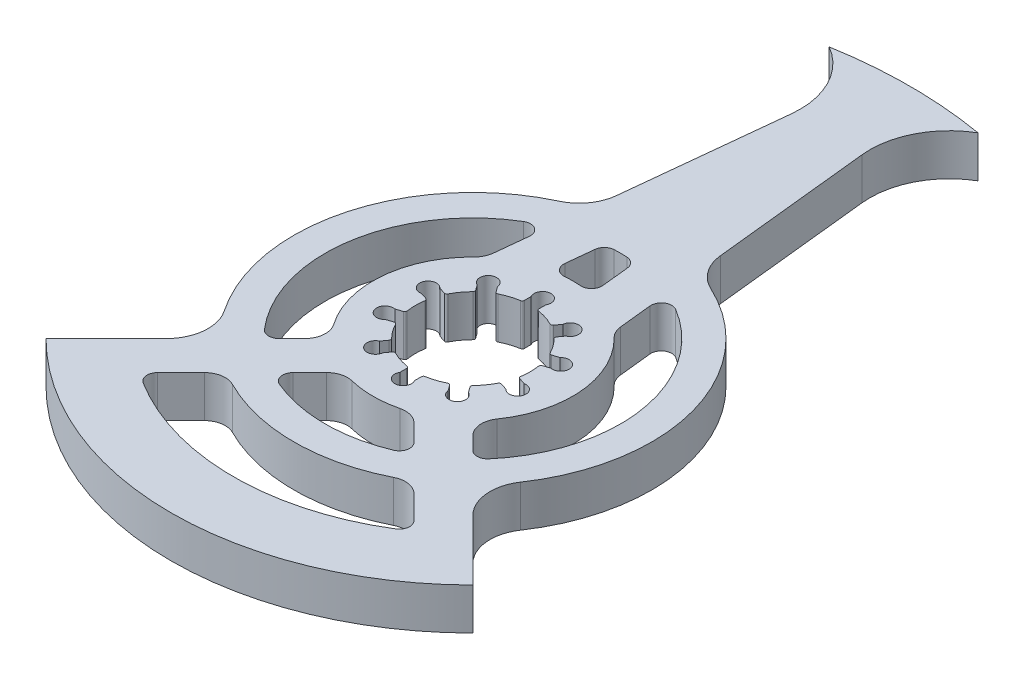
SolidWorks part; units mm, degrees
material "AISI Type A2 Tool Steel"
ref_plane "Front Plane" through (0, 0, 0) normal (0, 0, 1) x (1, 0, 0)
ref_plane "Top Plane" through (0, 0, 0) normal (0, 1, 0) x (1, 0, 0)
ref_plane "Right Plane" through (0, 0, 0) normal (1, 0, 0) x (0, 0, -1)
other "Center of Mass"
other "Bounding Box"
ref_plane "Default Plane" through (0, 2.286, 19.05) normal (0, -1, 0) x (-1, 0, 0)
sketch "Sketch1" plane through (0, 0, 0) normal (0, 1, 0) x (1, 0, 0)
  circle A0 centre (0, 0) radius 133.35 construction
  circle A1 centre (0, 0) radius 30.48
  circle A2 centre (0, 0) radius 17.4625
  dimension "D1" = 266.7
  dimension "D2" = 60.96
  dimension "D3" = 34.925
extrude "Boss-Extrude1" add sketch "Sketch1" along normal mid plane 12.7
sketch "Sketch2" plane through (0, 6.35, 0) normal (0, 1, 0) x (1, 0, 0)
  line L0 (-10.795, 107.95) -> (-19.6961, 23.2614)
  line L1 (19.6961, 23.2614) -> (10.795, 107.95)
  line L4 (0, 0) -> (0, 133.35) construction
  line L5 (-10.795, 107.95) -> (0, 107.95) construction
  line L6 (0, 107.95) -> (10.795, 107.95) construction
  line L7 (-22.6939, 131.4048) -> (0, 0) construction
  line L8 (-22.6939, 131.4048) -> (125.4677, 45.1673) construction
  circle A0 centre (0, 0) radius 133.35 construction
  circle A1 centre (0, 0) radius 133.35 construction
  arc A2 (-22.6939, 131.4048) -> (22.6939, 131.4048) centre (0, 0) cw
  arc A3 (-22.6939, 131.4048) -> (-10.795, 107.95) centre (-34.8727, 110.4807) cw
  circle A5 centre (0, 0) radius 30.48
  arc A6 (19.6961, 23.2614) -> (-19.6961, 23.2614) centre (0, 0) ccw
  arc A7 (-19.6961, 23.2614) -> (19.6961, 23.2614) centre (0, 0) ccw construction
  arc A8 (10.795, 107.95) -> (22.6939, 131.4048) centre (34.8727, 110.4807) cw
  dimension "D4" = 25.4
  dimension "D5" = 6
  dimension "D6" = 10.795
  dimension "D1" = 50
  dimension "D2" = 0
extrude "Boss-Extrude2" add sketch "Sketch2" against normal through all
sketch "Sketch3" plane through (0, 6.35, 0) normal (0, 1, 0) x (1, 0, 0)
  line L0 (-65.1069, -65.1069) -> (-21.5526, -21.5526)
  line L1 (21.5526, -21.5526) -> (65.1069, -65.1069)
  line L2 (0, -30.48) -> (0, -92.075) construction
  line L4 (-21.5526, -21.5526) -> (0, 0) construction
  line L5 (0, 0) -> (21.5526, -21.5526) construction
  arc A0 (-65.1069, -65.1069) -> (65.1069, -65.1069) centre (0, 0) ccw
  circle A1 centre (0, 0) radius 30.48 construction
  arc A3 (-21.5526, -21.5526) -> (21.5526, -21.5526) centre (0, 0) ccw
  point P13 (0, -92.075)
  dimension "D2" = 92.075
  dimension "D1" = 90
extrude "Boss-Extrude3" add sketch "Sketch3" against normal through all
sketch "Sketch5" plane through (0, 6.35, 0) normal (0, 1, 0) x (1, 0, 0)
  line L0 (0, 17.4625) -> (0, 21.2725) construction
  line L2 (-2.2225, 17.3205) -> (2.2225, 17.3205)
  line L3 (-2.2225, 17.3205) -> (-2.2225, 20.0168)
  line L5 (2.2225, 17.3205) -> (2.2225, 20.0168)
  arc A0 (2.2225, 20.0168) -> (-2.2225, 20.0168) centre (0, 21.2725) ccw
  circle A1 centre (0, 0) radius 17.4625 construction
  circle A2 centre (0, 21.2725) radius 4.5847 construction
  dimension "D2" = 5.1054
  dimension "D4" = 9.1694
  dimension "D1" = 3.81
  dimension "D3" = 4.445
extrude "Cut-Extrude2" cut sketch "Sketch5" against normal through all
pattern_circular "CirPattern1" count 10 over 360 about axis through (0, 6.35, 0) along (0, -1, 0) of "Cut-Extrude2"
sketch "Sketch6" plane through (0, 6.35, 0) normal (0, 1, 0) x (1, 0, 0)
  circle A0 centre (0, 0) radius 17.526
  arc A1 (-11.9788, 12.7062) -> (-15.786, 7.466) centre (0, 0) ccw construction
  dimension "D1" = 0.0635
extrude "Cut-Extrude3" cut sketch "Sketch6" against normal through all
sketch "Sketch7" plane through (0, 6.35, 0) normal (0, 1, 0) x (1, 0, 0)
  line L0 (-41.8693, -59.8298) -> (-10.6123, -28.5729)
  line L1 (10.6123, -28.5729) -> (41.8693, -59.8298)
  line L3 (-21.5526, -21.5526) -> (-65.1069, -65.1069) construction
  line L4 (65.1069, -65.1069) -> (21.5526, -21.5526) construction
  line L5 (-41.8693, -59.8298) -> (-50.8496, -50.8496) construction
  line L6 (41.8693, -59.8298) -> (50.8496, -50.8496) construction
  arc A0 (-10.6123, -28.5729) -> (10.6123, -28.5729) centre (0, 0) ccw
  arc A1 (-41.8693, -59.8298) -> (41.8693, -59.8298) centre (0, 0) ccw
  arc A2 (-65.1069, -65.1069) -> (65.1069, -65.1069) centre (0, 0) ccw construction
  arc A4 (21.5526, -21.5526) -> (19.6961, 23.2614) centre (0, 0) ccw construction
  dimension "D1" = 19.05
  dimension "D2" = 12.7
extrude "Cut-Extrude4" cut sketch "Sketch7" against normal through all
sketch "Sketch8" plane through (0, 6.35, 0) normal (0, 1, 0) x (1, 0, 0)
  circle A0 centre (0, 0) radius 45.085
  circle A1 centre (0, 0) radius 54.61
  dimension "D1" = 9.525
  dimension "D2" = 109.22
extrude "Boss-Extrude4" add sketch "Sketch8" against normal through all
sketch "Sketch11" plane through (0, 6.35, 0) normal (0, 1, 0) x (1, 0, 0)
  line L0 (-6.2352, 29.8354) -> (-4.6578, 44.8438)
  line L1 (4.6578, 44.8438) -> (6.2352, 29.8354)
  line L3 (-17.7867, 41.4281) -> (-19.6961, 23.2614) construction
  line L4 (19.6961, 23.2614) -> (17.7867, 41.4281) construction
  line L5 (-5.4465, 37.3396) -> (-18.0769, 38.6671) construction
  line L6 (5.4465, 37.3396) -> (18.0769, 38.6671) construction
  arc A0 (-6.2352, 29.8354) -> (6.2352, 29.8354) centre (0, 0) cw
  arc A1 (-4.6578, 44.8438) -> (4.6578, 44.8438) centre (0, 0) cw
  arc A2 (-19.6961, 23.2614) -> (-21.5526, -21.5526) centre (0, 0) ccw construction
  arc A3 (-17.7867, 41.4281) -> (-31.8799, -31.8799) centre (0, 0) ccw construction
  point P20 (-17.835, 38.1025)
  point P21 (-17.8345, 38.1025)
  dimension "D1" = 12.7
extrude "Cut-Extrude6" cut sketch "Sketch11" against normal through all
fillet "Fillet1" radius 6.35 8 edges at (-21.5526, 0, 21.5526) (21.5526, 0, 21.5526) (19.6961, 0, -23.2614) (-19.6961, 0, -23.2614) (10.6123, 0, 28.5729) (-10.6123, 0, 28.5729) (28.5761, 0, 46.5366) (-28.5761, 0, 46.5366)
fillet "Fillet6" radius 0.635 20 edges at (-12.0164, 0, -12.758) (-15.8469, 0, -7.4858) (-17.2204, 0, -3.2584) (-17.2204, 0, 3.2584) (-15.8469, 0, 7.4858) (-12.0164, 0, 12.758) (-8.4203, 0, 15.3707) (-2.2225, 0, 17.3845) (2.2225, 0, 17.3845) (8.4203, 0, 15.3707) (12.0164, 0, 12.758) (15.8469, 0, 7.4858) (17.2204, 0, 3.2584) (17.2204, 0, -3.2584) (15.8469, 0, -7.4858) (12.0164, 0, -12.758) (8.4203, 0, -15.3707) (2.2225, 0, -17.3845) (-2.2225, 0, -17.3845) (-8.4203, 0, -15.3707)
fillet "Fillet7" radius 3.175 12 edges at (-21.6087, 0, 39.5692) (21.6087, 0, 39.5692) (31.8799, 0, 31.8799) (-31.8799, 0, 31.8799) (-17.7867, 0, -41.4281) (17.7867, 0, -41.4281) (41.8693, 0, 59.8298) (-41.8693, 0, 59.8298) (-6.2352, 0, -29.8354) (6.2352, 0, -29.8354) (4.6578, 0, -44.8438) (-4.6578, 0, -44.8438)
fillet "Fillet8" radius 12.7 4 edges at (-16.6754, 0, -52.0018) (16.6754, 0, -52.0018) (38.6151, 0, 38.6151) (-38.6151, 0, 38.6151)
equation "\"Unit Measure\"= \"BoundingVolume\" / \"Thickness\"'in^2"
